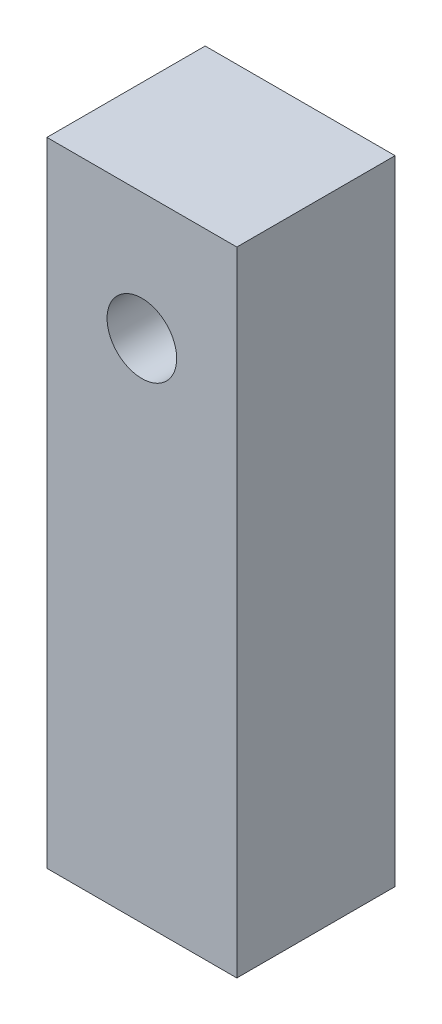
SolidWorks part; units mm, degrees
ref_plane "Front Plane" through (0, 0, 0) normal (0, 0, 1) x (1, 0, 0)
ref_plane "Top Plane" through (0, 0, 0) normal (0, 1, 0) x (1, 0, 0)
ref_plane "Right Plane" through (0, 0, 0) normal (1, 0, 0) x (0, 0, -1)
sketch "Sketch1" plane through (0, 0, 0) normal (0, 1, 0) x (1, 0, 0)
  line L0 (-2.0455, 4.4781) -> (3.9545, 4.4781)
  line L1 (3.9545, 4.4781) -> (3.9545, -0.5219)
  line L2 (3.9545, -0.5219) -> (-2.0455, -0.5219)
  line L3 (-2.0455, -0.5219) -> (-2.0455, 4.4781)
  dimension "D1" = 6
  dimension "D2" = 5
extrude "Boss-Extrude1" add sketch "Sketch1" along normal blind 20
sketch "Sketch2" plane through (0, 0, 0.5219) normal (0, 0, 1) x (1, 0, 0)
  line L0 (3.9545, 20) -> (3.9545, 0) construction
  line L1 (-2.0455, 0) -> (3.9545, 0) construction
  circle A0 centre (0.9545, 16) radius 1.1
  dimension "D1" = 2.2
  dimension "D2" = 3
  dimension "D3" = 16
extrude "Cut-Extrude1" cut sketch "Sketch2" against normal blind 20
